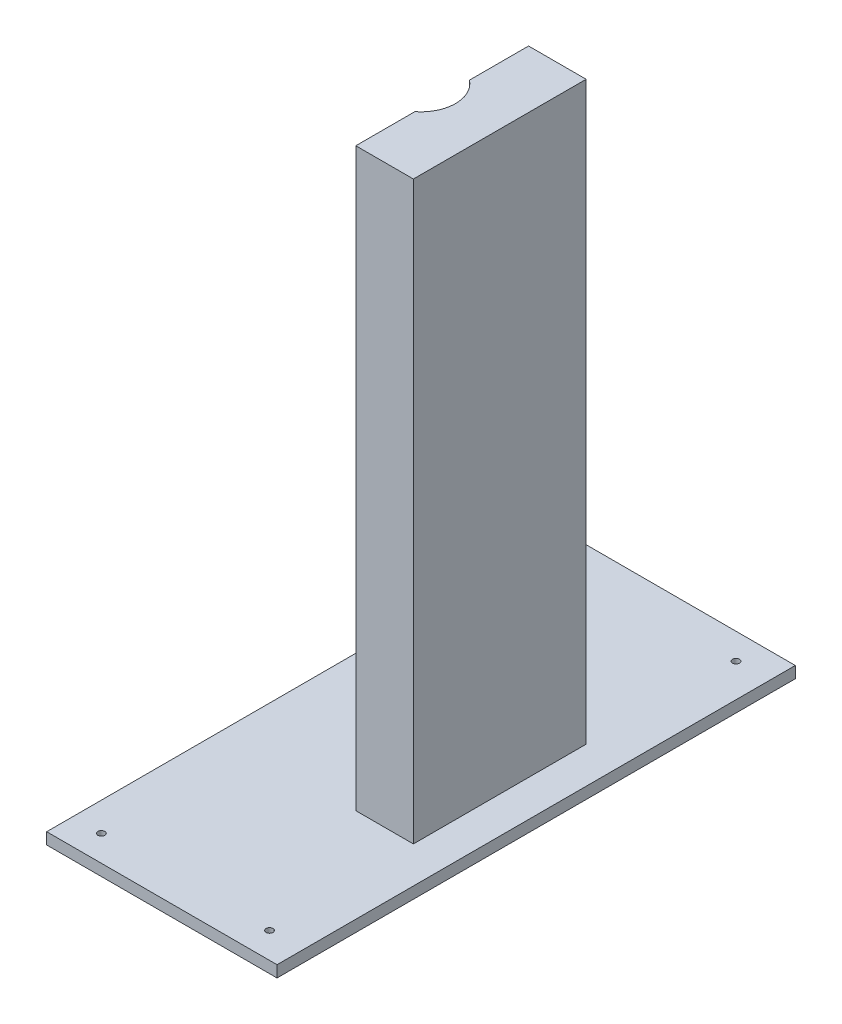
SolidWorks part; units mm, degrees
ref_plane "Front Plane" through (0, 0, 0) normal (0, 0, 1) x (1, 0, 0)
ref_plane "Top Plane" through (0, 0, 0) normal (0, 1, 0) x (1, 0, 0)
ref_plane "Right Plane" through (0, 0, 0) normal (1, 0, 0) x (0, 0, -1)
sketch "Sketch1" plane through (0, 0, 0) normal (0, 1, 0) x (1, 0, 0)
  line L0 (0, 0) -> (-100, 0) construction
  line L1 (100, -225) -> (-100, -225)
  line L2 (100, -225) -> (100, 225)
  line L3 (100, 225) -> (-100, 225)
  line L4 (-100, -225) -> (-100, 225)
  line L5 (100, -225) -> (-100, 225) construction
  line L6 (100, 225) -> (-100, -225) construction
  circle A0 centre (-75, 202.5) radius 3
  circle A1 centre (71, 202.5) radius 3
  circle A4 centre (71, -202.5) radius 3
  circle A5 centre (-75, -202.5) radius 3
  point P0 (0, 0)
  point P10 (71, -202.5)
  point P13 (-75, -202.5)
  dimension "D6" = 6
  dimension "D7" = 6
  dimension "D1" = 200
  dimension "D2" = 450
  dimension "D3" = 202.5
  dimension "D4" = 146
  dimension "D5" = 75
extrude "Boss-Extrude1" add sketch "Sketch1" along normal blind 10
sketch "Sketch2" plane through (0, 10, 0) normal (0, 1, 0) x (1, 0, 0)
  line L0 (0, 0) -> (-68.3943, 0)
  line L1 (-68.3943, 75) -> (-18.3943, 75) construction
  line L2 (-68.3943, 75) -> (-68.3943, -75) construction
  line L3 (-68.3943, -75) -> (-18.3943, -75) construction
  line L4 (-18.3943, 75) -> (-18.3943, 23.6992) construction
  line L5 (-18.3943, -26.007) -> (-18.3943, -75) construction
  line L6 (0, 0) -> (0, 31.8546) construction
  line L7 (18.3943, 23.6992) -> (18.3943, 75)
  line L9 (68.3943, -75) -> (18.3943, -75)
  line L10 (68.3943, 75) -> (18.3943, 75)
  line L11 (68.3943, 75) -> (68.3943, -75)
  line L12 (18.3943, -75) -> (18.3943, -23.6992)
  circle A3 centre (0, 0) radius 30
  point P7 (-68.3943, 0)
  dimension "D3" = 60
  dimension "D1" = 50
  dimension "D2" = 150
extrude "Boss-Extrude2" add sketch "Sketch2" along normal blind 300 contours L5 L4 L1 L2 L3 | A3 region at (26.1807, 10, -12.821)
extrude "Boss-Extrude3" add sketch "Sketch2<3>" along normal blind 500 contours A3 L12 L9 L11 L10 L7 region at (44.4874, 10, 0)
sketch "Sketch2<3>" plane through (0, 10, 0) normal (0, 1, 0) x (1, 0, 0) same geometry as "Sketch2"
